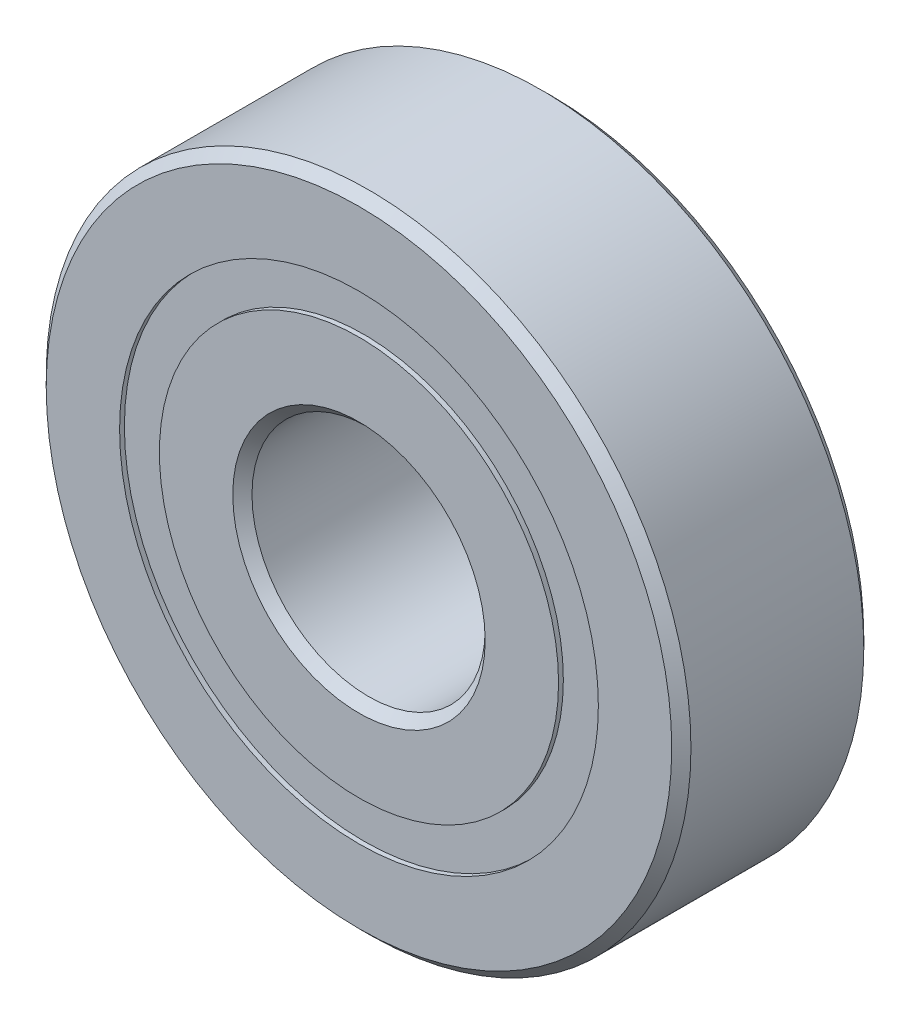
SolidWorks part; units mm, degrees
material "Alloy Steel"
ref_plane "Front Plane" through (0, 0, 0) normal (0, 0, 1) x (1, 0, 0)
ref_plane "Top Plane" through (0, 0, 0) normal (0, 1, 0) x (1, 0, 0)
ref_plane "Right Plane" through (0, 0, 0) normal (1, 0, 0) x (0, 0, -1)
sketch "Sketch1" plane through (0, 0, 0) normal (0, 0, 1) x (1, 0, 0)
  circle A0 centre (0, 0) radius 23.5 construction
  circle A1 centre (0, 0) radius 8.5 construction
  dimension "OD" = 47
  dimension "Shaft Dia" = 17
sketch "Sketch2" plane through (0, 0, 0) normal (1, 0, 0) x (0, 0, -1)
  line L0 (-7, 0) -> (7, 0) construction
  line L1 (0, 23.5) -> (0, -23.5) construction
  line L2 (6.3, 23.5) -> (-6.3, 23.5) construction
  line L3 (-6.3, 23.5) -> (-7, 22.8) construction
  line L4 (-7, 22.8) -> (-7, 17.4505) construction
  line L5 (-7, 17.4505) -> (-3.1111, 17.4505) construction
  line L6 (7, 17.4505) -> (3.1111, 17.4505) construction
  line L7 (7, 22.8) -> (7, 17.4505) construction
  line L8 (6.3, 23.5) -> (7, 22.8) construction
  line L9 (0, 23.5) -> (0, 16) construction
  line L10 (0, 16) -> (0, 8.5) construction
  line L11 (7, 16) -> (-7, 16) construction
  line L12 (-7, 9.2) -> (-7, 14.5495) construction
  line L13 (-6.3, 8.5) -> (-7, 9.2) construction
  line L14 (6.3, 8.5) -> (-6.3, 8.5) construction
  line L15 (6.3, 8.5) -> (7, 9.2) construction
  line L16 (7, 9.2) -> (7, 14.5495) construction
  line L17 (7, 14.5495) -> (3.1111, 14.5495) construction
  line L18 (-7, 14.5495) -> (-3.1111, 14.5495) construction
  arc A0 (-3.1111, 17.4505) -> (3.1111, 17.4505) centre (0, 16) cw construction
  arc A1 (-3.1111, 14.5495) -> (3.1111, 14.5495) centre (0, 16) ccw construction
  point P14 (0, 8.5)
  point P18 (0, 16)
  dimension "D1" = 45
  dimension "D2" = 0.7
  dimension "D3" = 6.2222
  dimension "D4" = 1.4505
  dimension "Width" = 14
sketch "Sketch6" plane through (0, 0, 0) normal (1, 0, 0) x (0, 0, -1)
  line L0 (-7, 22.8) -> (-7, 17.4505) construction
  line L1 (-6.3, 23.5) -> (-7, 22.8) construction
  line L2 (6.3, 23.5) -> (-6.3, 23.5) construction
  line L3 (6.3, 23.5) -> (7, 22.8) construction
  line L4 (7, 22.8) -> (7, 17.4505) construction
  line L5 (7, 17.4505) -> (3.1111, 17.4505) construction
  line L6 (-7, 17.4505) -> (-3.1111, 17.4505) construction
  line L7 (-7, 22.8) -> (-7, 17.4505)
  line L8 (-6.3, 23.5) -> (-7, 22.8)
  line L9 (6.3, 23.5) -> (-6.3, 23.5)
  line L10 (6.3, 23.5) -> (7, 22.8)
  line L11 (7, 22.8) -> (7, 17.4505)
  line L12 (7, 17.4505) -> (3.1111, 17.4505)
  line L13 (-7, 17.4505) -> (-3.1111, 17.4505)
  line L14 (-7, 9.2) -> (-7, 14.5495) construction
  line L15 (-6.3, 8.5) -> (-7, 9.2) construction
  line L16 (6.3, 8.5) -> (-6.3, 8.5) construction
  line L17 (6.3, 8.5) -> (7, 9.2) construction
  line L18 (7, 9.2) -> (7, 14.5495) construction
  line L19 (7, 14.5495) -> (3.1111, 14.5495) construction
  line L20 (-7, 14.5495) -> (-3.1111, 14.5495) construction
  line L21 (-7, 9.2) -> (-7, 14.5495)
  line L22 (-6.3, 8.5) -> (-7, 9.2)
  line L23 (6.3, 8.5) -> (-6.3, 8.5)
  line L24 (6.3, 8.5) -> (7, 9.2)
  line L25 (7, 9.2) -> (7, 14.5495)
  line L26 (7, 14.5495) -> (3.1111, 14.5495)
  line L27 (-7, 14.5495) -> (-3.1111, 14.5495)
  arc A0 (3.1111, 17.4505) -> (-3.1111, 17.4505) centre (0, 16) ccw construction
  arc A1 (3.1111, 17.4505) -> (-3.1111, 17.4505) centre (0, 16) ccw
  arc A2 (-3.1111, 14.5495) -> (3.1111, 14.5495) centre (0, 16) ccw construction
  arc A3 (-3.1111, 14.5495) -> (3.1111, 14.5495) centre (0, 16) ccw
revolve "Revolve1" add sketch "Sketch6" angle 360 about L0
sketch "Sketch4" plane through (0, 0, 0) normal (1, 0, 0) x (0, 0, -1)
  line L0 (-3.4327, 16) -> (3.4327, 16)
  arc A2 (-3.4327, 16) -> (3.4327, 16) centre (0, 16) cw
  arc A3 (3.1111, 17.4505) -> (-3.1111, 17.4505) centre (0, 16) ccw construction
revolve "Revolve2" add sketch "Sketch4" angle 360 about L0
ref_axis "Axis1" through (0, 0, -7) along (0, 0, 1)
pattern_circular "CirPattern1" count 12 every 30 about axis through (0, 0, -7) along (0, 0, 1) of bodies 104
sketch "Sketch5" plane through (0, 0, 0) normal (1, 0, 0) x (0, 0, -1)
  line L0 (-7, 17.4505) -> (-3.1111, 17.4505) construction
  line L1 (-6.65, 17.4505) -> (-3.4327, 17.4505)
  line L2 (-6.65, 17.4505) -> (-6.65, 14.5495)
  line L3 (-6.65, 14.5495) -> (-3.4327, 14.5495)
  line L4 (-3.4327, 17.4505) -> (-3.4327, 14.5495)
  line L6 (7, 17.4505) -> (3.1111, 17.4505) construction
  line L7 (6.65, 17.4505) -> (3.4327, 17.4505)
  line L8 (6.65, 17.4505) -> (6.65, 14.5495)
  line L9 (6.65, 14.5495) -> (3.4327, 14.5495)
  line L10 (3.4327, 17.4505) -> (3.4327, 14.5495)
  line L12 (-6.3, 23.5) -> (-7, 22.8) construction
  line L13 (-7, 14.5495) -> (-3.1111, 14.5495) construction
  line L14 (7, 14.5495) -> (3.1111, 14.5495) construction
  point P18 (-6.65, 23.15)
revolve "Revolve3" add sketch "Sketch5" angle 360 about L0
equation "\"D2@Sketch2\"= \"Width@Sketch2\" * .05"
equation "\"D3@Sketch2\"=\"Width@Sketch2\" / 2.25"
equation "\"D4@Sketch2\"= ( ( ( \"OD@Sketch1\" - \"Width@Sketch2\" ) / 2 ) / 3.25 ) / 3.5"
equation "\"D2@CirPattern1\" = 360/\"Balls@CirPattern1\""
